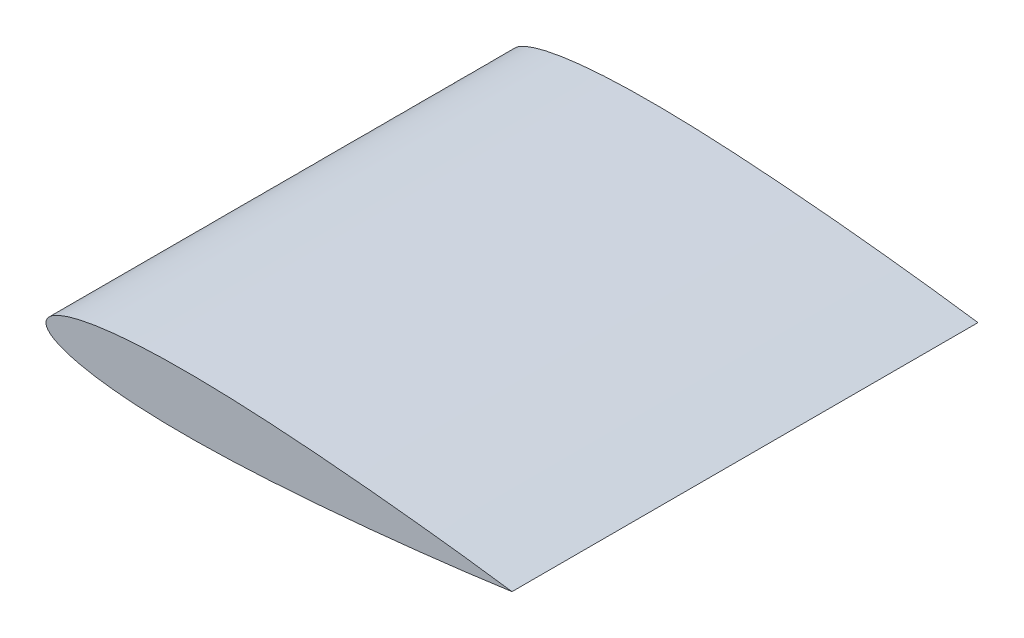
SolidWorks part; units mm, degrees
material "Custom Plastic"
ref_plane "Front Plane" through (0, 0, 0) normal (0, 0, 1) x (1, 0, 0)
ref_plane "Top Plane" through (0, 0, 0) normal (0, 1, 0) x (1, 0, 0)
ref_plane "Right Plane" through (0, 0, 0) normal (1, 0, 0) x (0, 0, -1)
other "Configuration Table"
sketch "Sketch1" plane through (0, 0, 0) normal (0, 0, -1) x (-1, 0, 0)
  spline S0 degree 4 poles (0, 0) (0, 0.0009) (0.0001, 0.0028) (0.0009, 0.006) (0.0029, 0.0097) (0.0068, 0.0145) (0.0126, 0.0192) (0.0211, 0.0244) (0.0349, 0.0306) (0.0554, 0.0375) (0.0898, 0.0455) (0.1398, 0.0529) (0.2034, 0.0579) (0.2766, 0.06) (0.3533, 0.0592) (0.4293, 0.0565) (0.5064, 0.052) (0.5813, 0.0466) (0.6596, 0.0397) (0.7322, 0.0327) (0.814, 0.0237) (0.8804, 0.0161) (0.9794, 0.0031) (1.0221, -0.003) (1.0781, -0.0115) (1.0995, -0.0151) knots 0 0 0 0 0 0.003159 0.007001 0.011626 0.014779 0.024842 0.033543 0.04731 0.068441 0.102186 0.159339 0.227558 0.295777 0.363996 0.432215 0.500435 0.568654 0.636873 0.705092 0.773311 0.84153 0.909749 1 1 1 1 1 construction
  spline S1 degree 4 poles (0, 0) (0, 0.0009) (0.0001, 0.0028) (0.0009, 0.006) (0.0029, 0.0097) (0.0068, 0.0145) (0.0126, 0.0192) (0.0211, 0.0244) (0.0349, 0.0306) (0.0554, 0.0375) (0.0898, 0.0455) (0.1398, 0.0529) (0.2034, 0.0579) (0.2766, 0.06) (0.3533, 0.0592) (0.4293, 0.0565) (0.5064, 0.052) (0.5813, 0.0466) (0.6596, 0.0397) (0.7322, 0.0327) (0.814, 0.0237) (0.8804, 0.0161) (0.9491, 0.0071) (0.9828, 0.0024) (1, 0) knots 0 0 0 0 0 0.003159 0.007001 0.011626 0.014779 0.024842 0.033543 0.04731 0.068441 0.102186 0.159339 0.227558 0.295777 0.363996 0.432215 0.500435 0.568654 0.636873 0.705092 0.773311 0.84153 0.909749 0.909749 0.909749 0.909749 0.909749
  spline S2 degree 4 poles (0, 0) (0, -0.0009) (0.0001, -0.0028) (0.0009, -0.006) (0.0029, -0.0097) (0.0068, -0.0145) (0.0126, -0.0192) (0.0211, -0.0244) (0.0349, -0.0306) (0.0554, -0.0375) (0.0898, -0.0455) (0.1398, -0.0529) (0.2034, -0.0579) (0.2766, -0.06) (0.3533, -0.0592) (0.4293, -0.0565) (0.5064, -0.052) (0.5813, -0.0466) (0.6596, -0.0397) (0.7322, -0.0327) (0.814, -0.0237) (0.8804, -0.0161) (0.9491, -0.0071) (0.9828, -0.0024) (1, 0) knots 0 0 0 0 0 0.003159 0.007001 0.011626 0.014779 0.024842 0.033543 0.04731 0.068441 0.102186 0.159339 0.227558 0.295777 0.363996 0.432215 0.500435 0.568654 0.636873 0.705092 0.773311 0.84153 0.909749 0.909749 0.909749 0.909749 0.909749
extrude "Boss-Extrude1" add sketch "Sketch1" against normal mid plane 1 contours S1 S2
scale "Scale1" bodies to scale 133 scale about origin uniform scaling yes scale factor 1000
mirror "Mirror2" about plane through (0, 0, 0) normal (1, 0, 0) of bodies 134
delete or keep bodies "Body-Delete/Keep 1" type delete bodies bodies 134
move or copy body "Body-Move/Copy1" bodies to move or copy 135 copy no translate (-500, 0, 0) parameters "D1"=500, "D2"=0, "D3"=0
sketch "Sketch2" plane through (0, 0, 0) normal (0, 0, 1) x (1, 0, 0)
  line L0 (-500, 0) -> (500, 0)
  line L1 (-500, 2.1833) -> (-500, -2.1833) construction
  spline S0 degree 4 poles (2478.7272, -289.2445) (423.1719, 8.4831) (643.6673, -19.7059) (440.8817, 9.128) (313.9835, 23.6951) (232.2353, 32.72) (159.6226, 39.6686) (81.3387, 46.5686) (6.3787, 51.9966) (-70.7422, 56.4931) (-146.6597, 59.2334) (-223.4368, 60.0011) (-296.5712, 57.927) (-360.2447, 52.9024) (-410.1717, 45.5098) (-444.5688, 37.4554) (-465.1338, 30.5916) (-478.8896, 24.4285) (-487.4431, 19.2162) (-493.2259, 14.4571) (-497.0581, 9.7135) (-508.1307, -10.6702) (-483.3348, -44.4778) (-363.7802, 8.8731) (-1620.7208, -1653.5185) knots -0.248501 -0.248501 -0.248501 -0.248501 -0.248501 0.068219 0.136438 0.204657 0.272877 0.341096 0.409315 0.477534 0.545753 0.613972 0.682191 0.750411 0.807563 0.841309 0.862439 0.876207 0.884907 0.894971 0.898124 0.902749 0.90659 0.977003 0.977003 0.977003 0.977003 0.977003 only from (500, 0) to (-500, 0)
  spline S1 degree 4 poles (500, 0) (482.7842, 2.4425) (449.0757, 7.0543) (380.3991, 16.071) (313.9835, 23.6951) (232.2353, 32.72) (159.6226, 39.6686) (81.3387, 46.5686) (6.3787, 51.9966) (-70.7422, 56.4931) (-146.6597, 59.2334) (-223.4368, 60.0011) (-296.5712, 57.927) (-360.2447, 52.9024) (-410.1717, 45.5098) (-444.5688, 37.4554) (-465.1338, 30.5916) (-478.8896, 24.4285) (-487.4431, 19.2162) (-493.2259, 14.4571) (-497.0581, 9.7135) (-499.0529, 6.0412) (-499.8522, 2.8438) (-500.0001, 0.8885) (-500, 0) knots 0 0 0 0 0 0.068219 0.136438 0.204657 0.272877 0.341096 0.409315 0.477534 0.545753 0.613972 0.682191 0.750411 0.807563 0.841309 0.862439 0.876207 0.884907 0.894971 0.898124 0.902749 0.90659 0.909749 0.909749 0.909749 0.909749 0.909749 construction
  spline S2 degree 3 poles (-500, 0) (-500, 2.7291) (-498.5529, 7.8775) (-491.6299, 16.5451) (-479.1222, 24.5276) (-462.4123, 31.5752) (-444.0284, 37.302) (-426.2061, 41.6376) (-408.6366, 45.1359) (-390.8655, 48.1122) (-372.8458, 50.6038) (-353.7061, 52.7976) (-335.2387, 54.5401) (-317.4586, 55.9014) (-300.2838, 56.9849) (-284.9238, 57.7627) (-269.2711, 58.3919) (-255.0597, 58.8369) (-239.4499, 59.1888) (-222.3611, 59.4282) (-203.6224, 59.5158) (-183.1564, 59.4267) (-162.2935, 59.1568) (-141.7213, 58.7231) (-123.0433, 58.2003) (-105.6398, 57.6135) (-85.0076, 56.8071) (-64.7727, 55.8764) (-43.0346, 54.7492) (-25.0677, 53.7336) (-5.5209, 52.5446) (16.6389, 51.1121) (40.3772, 49.4602) (64.5521, 47.6532) (86.1415, 45.9469) (106.498, 44.2562) (128.8558, 42.3267) (151.4446, 40.3072) (175.3817, 38.0929) (198.7194, 35.8635) (222.5053, 33.5002) (246.4395, 31.021) (267.4122, 28.7765) (286.9467, 26.6415) (306.1913, 24.5048) (325.8575, 22.2823) (345.1735, 20.052) (363.4287, 17.888) (383.3057, 15.4612) (402.4966, 13.0493) (421.5184, 10.604) (439.7071, 8.226) (457.5741, 5.85) (477.9418, 3.091) (491.5939, 1.1929) (500, 0) knots 0 0 0 0 0.00761 0.015629 0.031917 0.050723 0.068938 0.088517 0.104683 0.121651 0.141539 0.158212 0.178345 0.196126 0.210691 0.228991 0.241388 0.256794 0.270835 0.287339 0.307091 0.325983 0.347571 0.368495 0.386541 0.402562 0.419743 0.447308 0.462176 0.483805 0.500269 0.519809 0.549158 0.5703 0.591154 0.612894 0.630416 0.657198 0.679639 0.701164 0.726195 0.749986 0.77198 0.78827 0.807818 0.828966 0.846517 0.865043 0.883067 0.90545 0.921967 0.93951 0.959435 0.975013 1 1 1 1
  point P3 (0, 0)
  point P9 (0, 0)
  point P11 (0, 0)
extrude "Boss-Extrude2" add sketch "Sketch2" along normal mid plane 1000 separate body
delete or keep bodies "Body-Delete/Keep 2" type delete bodies bodies 140
mirror "Mirror3" about plane through (0, 0, 0) normal (0, 1, 0) of bodies 141
